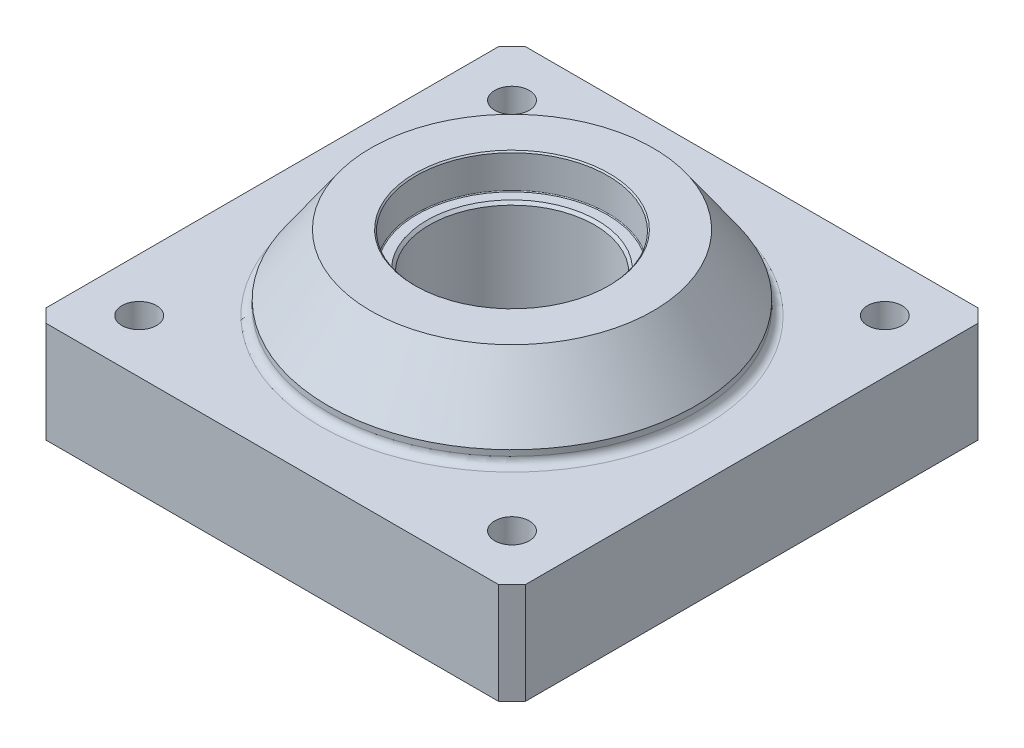
SolidWorks part; units mm, degrees
ref_plane "Front" through (0, 0, 0) normal (0, 0, 1) x (1, 0, 0)
ref_plane "Top" through (0, 0, 0) normal (0, 1, 0) x (1, 0, 0)
ref_plane "Right" through (0, 0, 0) normal (1, 0, 0) x (0, 0, -1)
ref_axis "Axis1" through (-84.4107, 0, 0) along (1, 0, 0)
ref_axis "Axis2" through (0, 64.3378, 0) along (0, -1, 0)
ref_axis "Axis3" through (0, 0, -102.329) along (0, 0, 1)
sketch "Sketch1" plane through (0, 0, 0) normal (0, 1, 0) x (1, 0, 0)
  line L1 (-90, 90) -> (90, 90)
  line L2 (-90, 90) -> (-90, -90)
  line L3 (-90, -90) -> (90, -90)
  line L4 (90, 90) -> (90, -90)
  point P4 (0, 90)
  point P6 (90, 0)
  dimension "D1" = 180
  dimension "D2" = 180
extrude "Boss-Extrude1" add sketch "Sketch1" along normal blind 38 contours L1 L4 L3 L2
sketch "Sketch2" plane through (0, 38, 0) normal (0, 1, 0) x (1, 0, 0)
  circle A0 centre (0, 0) radius 69
  dimension "D1" = 138
extrude "Boss-Extrude2" add sketch "Sketch2" along normal blind 28
sketch "Sketch3" plane through (0, 66, 0) normal (0, 1, 0) x (1, 0, 0)
  circle A0 centre (0, 0) radius 53
  circle A1 centre (0, 0) radius 36
  dimension "D1" = 106
chamfer "Chamfer3" distance 16 angle 55 1 edges at (0, 66, 69) first distance on face at (0, 66, 69)
extrude "Cut-Extrude1" cut sketch "Sketch3" against normal blind 13 contours A1
sketch "Sketch4" plane through (0, 0, 0) normal (0, -1, 0) x (-1, 0, 0)
  circle A0 centre (0, 0) radius 31
extrude "Cut-Extrude2" cut sketch "Sketch4" against normal up to next contours A0
sketch "Sketch5" plane through (0, 38, 0) normal (0, 1, 0) x (1, 0, 0)
  line L0 (-90, -90) -> (-90, -70)
  line L1 (-90, 90) -> (-90, -90) construction
  line L2 (-90, -70) -> (69.2663, -70)
  line L3 (-90, -90) -> (-70, -90)
  line L4 (-90, -90) -> (90, -90) construction
  line L5 (-70, -90) -> (-70, 70)
  line L6 (-70, 70) -> (69.2663, 70)
  circle A0 centre (-70, 70) radius 6.5
extrude "Cut-Extrude3" cut sketch "Sketch5" against normal up to next contours A0
pattern_linear "LPattern1" count 2 spacing 140 along (1, 0, 0) count 2 spacing 140 along (0, 0, 1) of "Cut-Extrude3"
ref_axis "Axis5" through (-70, 0, 70) along (0, 1, 0)
chamfer "Chamfer4" distance 5 angle 45 4 edges at (-90, 19, -90) (90, 19, -90) (-90, 19, 90) (90, 19, 90)
chamfer "Chamfer5" distance 1 angle 45 2 edges at (0, 0, -31) (0, 53, 31)
chamfer "Chamfer6" distance 0.5 angle 45 1 edges at (0, 66, 36)
fillet "Fillet1" radius 0.3 1 edges at (0, 53, 36)
fillet "Fillet2" radius 3 1 edges at (0, 38, 69)
